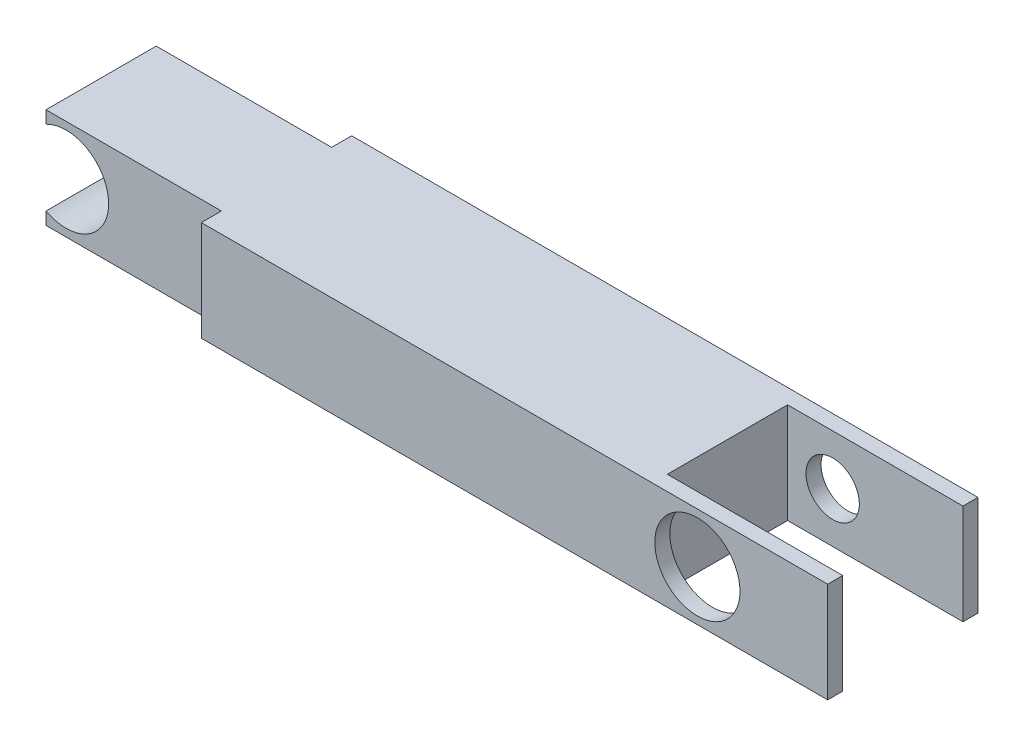
SolidWorks part; units mm, degrees
ref_plane "Front Plane" through (0, 0, 0) normal (0, 0, 1) x (1, 0, 0)
ref_plane "Top Plane" through (0, 0, 0) normal (0, 1, 0) x (1, 0, 0)
ref_plane "Right Plane" through (0, 0, 0) normal (1, 0, 0) x (0, 0, -1)
sketch "Sketch2" plane through (0, 0, 0) normal (0, 0, 1) x (1, 0, 0)
  line L0 (-72.5199, -2.2752) -> (-72.5199, -7.3552)
  line L1 (-72.5199, -7.3552) -> (-31.8799, -7.3552)
  line L2 (-31.8799, -7.3552) -> (-31.8799, -2.2752)
  line L3 (-31.8799, -2.2752) -> (-72.5199, -2.2752)
  dimension "D1" = 40.64
  dimension "D2" = 5.08
extrude "Boss-Extrude1" add sketch "Sketch2" along normal blind 7.62
sketch "Sketch6" plane through (0, 0, 7.62) normal (0, 0, 1) x (1, 0, 0)
  line L0 (-31.8799, -7.3552) -> (-31.8799, -2.2752) construction
  point P0 (-71.5039, -4.8152)
  point P1 (-38.4839, -4.8152)
  point P6 (0, 0)
  dimension "D2" = 6.604
  dimension "D3" = 33.02
sketch "Sketch7" plane through (0, -7.3552, 0) normal (0, -1, 0) x (1, 0, 0)
  line L0 (-31.8799, 0.762) -> (-40.7699, 0.762)
  line L1 (-31.8799, 7.62) -> (-31.8799, 0) construction
  line L2 (-40.7699, 0.762) -> (-40.7699, 6.858)
  line L3 (-40.7699, 6.858) -> (-31.8799, 6.858)
  line L4 (-31.8799, 6.858) -> (-31.8799, 0.762)
  line L5 (-72.5199, 0) -> (-31.8799, 0) construction
  line L6 (-72.5199, 7.62) -> (-31.8799, 7.62) construction
  line L7 (-72.5199, 0) -> (-63.6299, 0)
  line L8 (-63.6299, 0) -> (-63.6299, 1.016)
  line L9 (-63.6299, 1.016) -> (-72.5199, 1.016)
  line L10 (-72.5199, 7.62) -> (-72.5199, 0) construction
  line L11 (-72.5199, 1.016) -> (-72.5199, 6.604)
  line L12 (-72.5199, 6.604) -> (-63.6299, 6.604)
  line L13 (-63.6299, 6.604) -> (-63.6299, 7.62)
  line L14 (-63.6299, 7.62) -> (-72.5199, 7.62)
  line L15 (-72.5199, 7.62) -> (-72.5199, 0)
  line M7 (-72.5199, 0) -> (-31.8799, 0)
  line M8 (-31.8799, 0) -> (-31.8799, 7.62)
  line M9 (-31.8799, 7.62) -> (-72.5199, 7.62)
  line M10 (-72.5199, 7.62) -> (-72.5199, 0)
  dimension "D1" = 8.89
  dimension "D2" = 0.762
  dimension "D3" = 0.762
  dimension "D4" = 1.016
  dimension "D5" = 1.016
  dimension "D6" = 8.89
  dimension "D7" = 8.89
extrude "Cut-Extrude2" cut sketch "Sketch7" against normal through all contours L3 L2 L0 M8 | L8 L9 M10 M7 | L12 L13 M9 M10 region at (-36.3249, -7.3552, 3.81) region at (-68.0749, -7.3552, 0.508) region at (-68.0749, -7.3552, 7.112)
sketch "Sketch8" plane through (0, 0, 7.62) normal (0, 0, 1) x (1, 0, 0)
  circle A0 centre (-38.4839, -4.8152) radius 2.159
  dimension "D1" = 4.318
extrude "Cut-Extrude3" cut sketch "Sketch8" against normal up to next
sketch "Sketch9" plane through (0, 0, 6.604) normal (0, 0, 1) x (1, 0, 0)
  circle A0 centre (-71.5039, -4.8152) radius 2.159
  dimension "D1" = 4.318
extrude "Cut-Extrude4" cut sketch "Sketch9" against normal through all
hole_wizard "#6-32 Tapped Hole1" positions "Sketch11" profile "Sketch12" tap size "#6-32" standard "ANSI Inch" end condition up to next
sketch "Sketch11" plane through (0, 0, 0) normal (0, 0, -1) x (-1, 0, 0)
  point P0 (38.4839, -4.8152)
sketch "Sketch12" plane through (-38.4839, -4.8152, 0) normal (1, 0, 0) x (0, 1, 0)
  line L0 (0, 0) -> (0, 0.762)
  line L1 (0, 0.762) -> (1.3525, 0.762)
  line L2 (1.3525, 0.762) -> (1.3525, 0)
  line L5 (1.3525, 0) -> (0, 0)
  line L11 (0, -6.35) -> (0, 107.95) construction
  dimension "Thread Major Dia." = 2.7051
  dimension "Thru Tap Drill Depth" = 0.762
ref_plane "Plane1" through (0, -4.8152, 0) normal (0, 1, 0) x (1, 0, 0)
ref_plane "Plane2" through (0, 0, 3.81) normal (0, 0, -1) x (-1, 0, 0)
